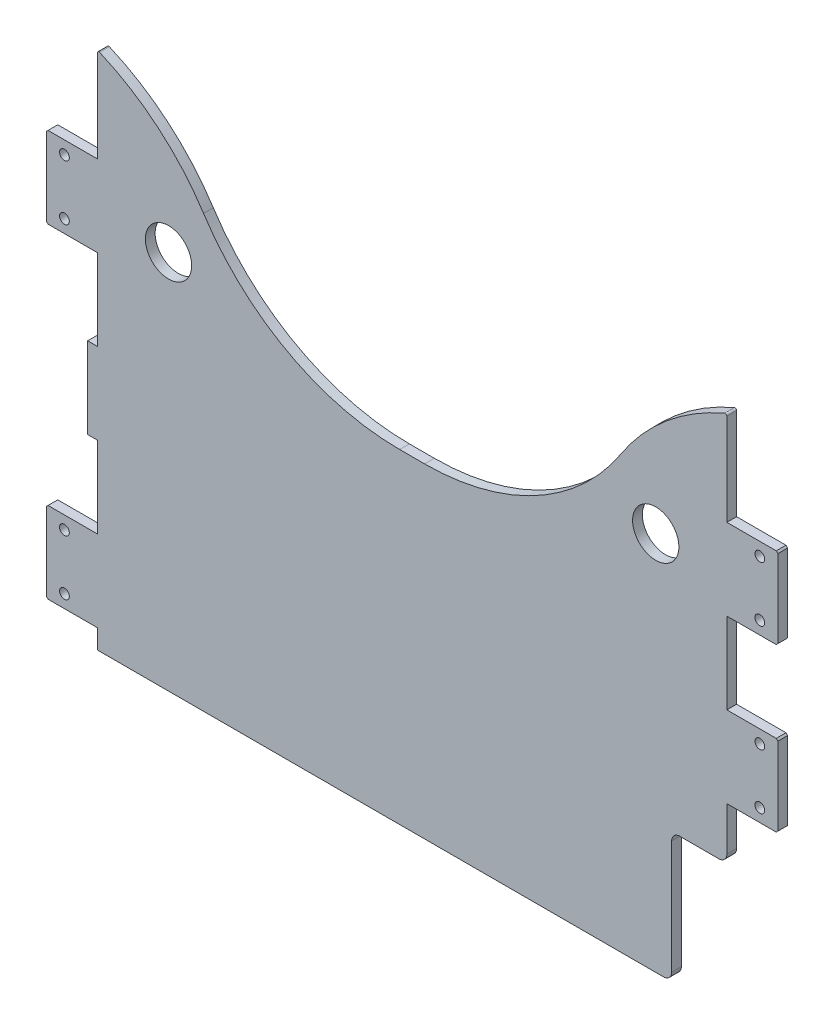
SolidWorks part; units mm, degrees
material "ABS PC"
ref_plane "Plano frontal" through (0, 0, 0) normal (0, 0, 1) x (1, 0, 0)
ref_plane "Plano superior" through (0, 0, 0) normal (0, 1, 0) x (1, 0, 0)
ref_plane "Plano direito" through (0, 0, 0) normal (1, 0, 0) x (0, 0, -1)
sketch "Esboço1" plane through (0, 0, 0) normal (0, 0, 1) x (1, 0, 0)
  line L1 (0, 0) -> (387.6, 0)
  line L2 (0, 0) -> (0, 320)
  line L3 (0, 320) -> (387.6, 320)
  line L4 (387.6, 0) -> (387.6, 320)
  dimension "D1" = 387.6
  dimension "D2" = 320
extrude "Ressalto-extrusão1" add sketch "Esboço1" along normal blind 6
sketch "Esboço2" plane through (0, 0, 6) normal (0, 0, 1) x (1, 0, 0)
  line L0 (33.8, 320) -> (103.8, 200)
  line L1 (103.8, 200) -> (283.8, 200)
  line L2 (283.8, 200) -> (353.8, 320)
  line L3 (387.6, 320) -> (0, 320) construction
  line L4 (353.8, 320) -> (33.8, 320)
  line L5 (193.8, 200) -> (193.8, 0) construction
  line L6 (0, 0) -> (387.6, 0) construction
  line L7 (33.8, 320) -> (0, 320) construction
  line L8 (353.8, 320) -> (387.6, 320) construction
  dimension "D1" = 320
  dimension "D2" = 200
  dimension "D3" = 180
extrude "Corte-extrusão1" cut sketch "Esboço2" against normal through all
sketch "Esboço3" plane through (0, 0, 6) normal (0, 0, 1) x (1, 0, 0)
  line L0 (193.8, 200) -> (193.8, 0) construction
  line L1 (103.8, 200) -> (283.8, 200) construction
  line L2 (0, 0) -> (387.6, 0) construction
  line L3 (33.8, 320) -> (0, 320) construction
  circle A0 centre (43.8, 234) radius 14.25
  circle A1 centre (343.8, 234) radius 14.25
  dimension "D3" = 28.5
  dimension "D1" = 86
  dimension "D2" = 300
extrude "Corte-extrusão2" cut sketch "Esboço3" against normal through all
fillet "Filete1" radius 144 2 edges at (353.8, 320, 3) (33.8, 320, 3)
fillet "Filete2" radius 144 2 edges at (283.8, 200, 3) (103.8, 200, 3)
ref_plane "Plano1" through (193.8, 0, 0) normal (-1, 0, 0) x (0, 0, 1)
sketch "Esboço4" plane through (0, 0, 0) normal (-1, 0, 0) x (0, 0, 1)
  line L0 (6, 261.903) -> (6, 211.903)
  line L1 (6, 261.903) -> (0, 261.903)
  line L2 (6, 211.903) -> (0, 211.903)
  line L3 (0, 261.903) -> (0, 211.903)
  line L4 (6, 320) -> (6, 0) construction
  line L6 (6, 161.903) -> (6, 111.903)
  line L7 (6, 161.903) -> (0, 161.903)
  line L8 (6, 111.903) -> (0, 111.903)
  line L9 (0, 161.903) -> (0, 111.903)
  line L10 (6, 61.903) -> (6, 11.903)
  line L11 (6, 61.903) -> (0, 61.903)
  line L12 (6, 11.903) -> (0, 11.903)
  line L13 (0, 61.903) -> (0, 11.903)
  line L14 (0, 320) -> (0, 0) construction
  point P6 (0, 0)
  point P17 (0, 0)
  point P18 (0, 0)
extrude "Ressalto-extrusão2" add sketch "Esboço4" along normal blind 31.4
mirror "Espelhar1" about plane through (193.8, 0, 0) normal (-1, 0, 0) of "Ressalto-extrusão2"
sketch "Esboço5" plane through (0, 0, 6) normal (0, 0, 1) x (1, 0, 0)
  line L0 (419, 11.903) -> (387.6, 11.903) construction
  line L1 (419, 61.903) -> (393.6, 61.903)
  line L2 (419, 61.903) -> (419, 11.903)
  line L3 (419, 11.903) -> (393.6, 11.903)
  line L4 (393.6, 61.903) -> (393.6, 11.903)
  line L5 (387.6, 61.903) -> (387.6, 111.903) construction
  line L6 (-31.4, 111.903) -> (0, 111.903) construction
  line L7 (-31.4, 161.903) -> (-6, 161.903)
  line L8 (-31.4, 161.903) -> (-31.4, 111.903)
  line L9 (-31.4, 111.903) -> (-6, 111.903)
  line L10 (-6, 161.903) -> (-6, 111.903)
  line L11 (0, 211.903) -> (0, 161.903) construction
  dimension "D1" = 6
  dimension "D2" = 6
extrude "Corte-extrusão3" cut sketch "Esboço5" against normal through all
sketch "Esboço6" plane through (0, 0, 6) normal (0, 0, 1) x (1, 0, 0)
  line L0 (0, 0) -> (387.6, 0) construction
  line L1 (353.6, 0) -> (393.6, 0)
  line L2 (353.6, 0) -> (353.6, 80)
  line L3 (353.6, 80) -> (393.6, 80)
  line L4 (393.6, 0) -> (393.6, 80)
  point P6 (0, 0)
  dimension "D1" = 80
  dimension "D2" = 40
extrude "Corte-extrusão4" cut sketch "Esboço6" against normal through all
fillet "Filete3" radius 5 3 edges at (353.6, 80, 3) (353.6, 0, 3) (387.6, 80, 3)
chamfer "Chanfro1" distance 1 angle 45 8 edges at (-31.4, 211.903, 3) (-31.4, 261.903, 3) (419, 261.903, 3) (419, 211.903, 3) (419, 161.903, 3) (419, 111.903, 3) (-31.4, 61.903, 3) (-31.4, 11.903, 3)
fillet "Filete4" radius 1 2 edges at (0, 320, 3) (387.6, 320, 3)
sketch "Esboço8" plane through (0, 0, 6) normal (0, 0, 1) x (1, 0, 0)
  circle A0 centre (407.9, 253.903) radius 3
  circle A1 centre (407.9, 219.903) radius 3
  circle A2 centre (407.9, 153.903) radius 3
  circle A3 centre (407.9, 119.903) radius 3
  circle A4 centre (-20.3, 19.903) radius 3
  circle A5 centre (-20.3, 53.903) radius 3
  circle A6 centre (-20.3, 219.903) radius 3
  circle A7 centre (-20.3, 253.903) radius 3
extrude "Corte-extrusão5" cut sketch "Esboço8" against normal through all
